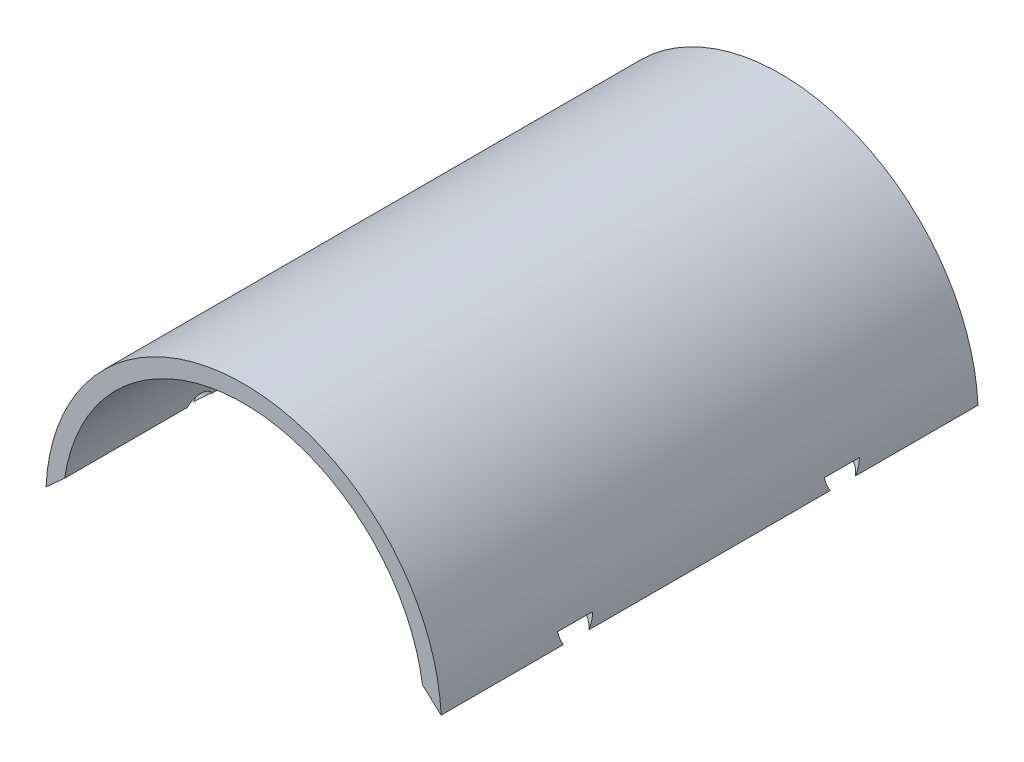
SolidWorks part; units mm, degrees
ref_plane "Front Plane" through (0, 0, 0) normal (0, 0, 1) x (1, 0, 0)
ref_plane "Top Plane" through (0, 0, 0) normal (0, 1, 0) x (1, 0, 0)
ref_plane "Right Plane" through (0, 0, 0) normal (1, 0, 0) x (0, 0, -1)
sketch "Sketch1" plane through (0, 0, 0) normal (0, 0, 1) x (1, 0, 0)
  line L0 (0, 0) -> (0, 44.45) construction
  line L1 (-40.2039, 5.9378) -> (40.2039, 5.9378) construction
  line L2 (-44.399, 2.1278) -> (44.399, 2.1278) construction
  line L3 (-40.2039, 5.9378) -> (-44.399, 2.1278)
  line L4 (40.2039, 5.9378) -> (44.399, 2.1278)
  arc A0 (44.399, 2.1278) -> (-44.399, 2.1278) centre (0, 0) ccw
  arc A1 (40.2039, 5.9378) -> (-40.2039, 5.9378) centre (0, 0) ccw
  dimension "D1" = 88.9
  dimension "D2" = 3.81
  dimension "D3" = 3.81
extrude "Boss-Extrude1" add sketch "Sketch1" along normal blind 120.65
sketch "Sketch2" plane through (-21.1272, 23.263, 0) normal (0.6723, -0.7403, 0) x (0.7403, 0.6723, 0)
  line L0 (-28.6033, 120.65) -> (-28.6033, 0.0141) construction
  line L1 (-31.4368, 120.65) -> (-25.7698, 120.65) construction
  line L2 (-31.4368, 60.325) -> (-25.7698, 60.325) construction
  line L3 (-31.4368, 120.65) -> (-31.4368, 0) construction
  line L4 (-25.7698, 120.65) -> (-25.7698, 0) construction
  circle A0 centre (-28.6033, 90.297) radius 4
  circle A1 centre (-28.6033, 30.353) radius 4
  dimension "D1" = 8
  dimension "D2" = 29.972
extrude "Cut-Extrude1" cut sketch "Sketch2" against normal blind 2
sketch "Sketch3" plane through (21.1272, 23.263, 0) normal (-0.6723, -0.7403, 0) x (0.7403, -0.6723, 0)
  line L0 (28.6033, 120.65) -> (28.6033, 0.2465) construction
  line L1 (25.7698, 120.65) -> (31.4368, 120.65) construction
  line L2 (25.7698, 60.325) -> (31.4368, 60.325) construction
  line L3 (25.7698, 120.65) -> (25.7698, 0) construction
  line L4 (31.4368, 120.65) -> (31.4368, 0) construction
  circle A0 centre (28.6033, 90.297) radius 4
  circle A1 centre (28.6033, 30.353) radius 4
  dimension "D1" = 8
  dimension "D2" = 29.972
extrude "Cut-Extrude2" cut sketch "Sketch3" against normal blind 2
